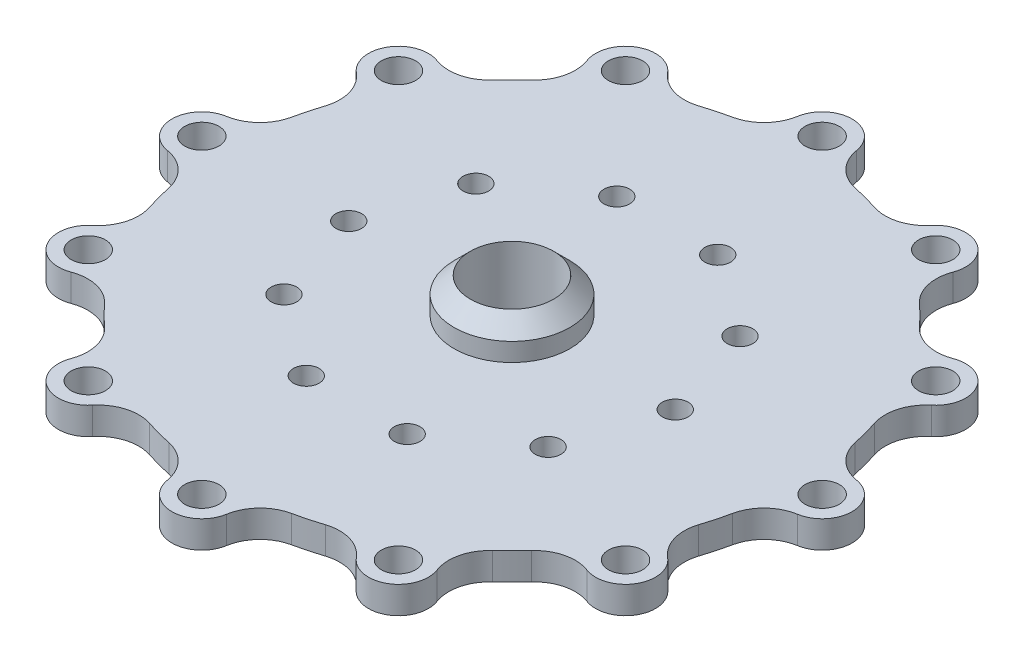
SolidWorks part; units mm, degrees
material "Nickel"
ref_plane "Front Plane" through (0, 0, 0) normal (0, 0, 1) x (1, 0, 0)
ref_plane "Top Plane" through (0, 0, 0) normal (0, 1, 0) x (1, 0, 0)
ref_plane "Right Plane" through (0, 0, 0) normal (1, 0, 0) x (0, 0, -1)
sketch "Sketch1" plane through (0, 0, 0) normal (0, 0, 1) x (1, 0, 0)
  line L0 (79.375, 10.6858) -> (79.375, 17.0358)
  line L1 (0, 0) -> (0, 52.0897) construction
  line L3 (79.375, 10.6858) -> (19.2253, 10.6858)
  line L4 (79.375, 17.0358) -> (13.5204, 17.0358)
  line L5 (9.7104, 25.1308) -> (9.7104, 0)
  line L6 (14.1453, -4.4348) -> (19.2253, -4.4348)
  line L10 (19.2253, -4.4348) -> (19.2253, 10.6858)
  line L11 (9.7104, 25.1308) -> (13.5204, 25.1308)
  line L12 (13.5204, 25.1308) -> (13.5204, 17.0358)
  line L15 (14.1453, -4.4348) -> (9.7104, 0)
  dimension "D1" = 79.375
  dimension "D2" = 9.7104
  dimension "D3" = 15.1206
  dimension "D4" = 6.35
  dimension "D5" = 19.2253
  dimension "D8" = 135
  dimension "D9" = 5.08
  dimension "D10" = 3.81
  dimension "D11" = 8.095
revolve "Revolve1" add sketch "Sketch1" angle 360 about L1
chamfer "Chamfer1" distance 3.81 angle 45 1 edges at (13.5204, 25.1308, 0)
hole_wizard "Hole2" positions "Sketch5" profile "Sketch6" legacy end condition up to next
sketch "Sketch5" plane through (0, 17.0358, 0) normal (0, 1, 0) x (1, 0, 0)
  line L0 (0, 0) -> (38.1, 0) construction
  point P0 (38.1, 0)
  dimension "D1" = 38.1
sketch "Sketch6" plane through (38.1, 17.0358, 0) normal (1, 0, 0) x (0, 0, 1)
  line L0 (0, 0) -> (0, 6.351)
  line L1 (0, 6.351) -> (3, 6.351)
  line L2 (3, 6.351) -> (3, 0)
  line L3 (3, 0) -> (0, 0)
  line L4 (0, 110) -> (0, -10) construction
  dimension "Diameter" = 6
  dimension "Depth" = 6.351
pattern_circular "CirPattern2" count 10 over 360 about axis through (0, 0, 0) along (0, 1, 0) of "Hole2"
hole_wizard "Hole4" positions "Sketch11" profile "Sketch13" legacy
sketch "Sketch11" plane through (0, 10.6858, 0) normal (0, 1, 0) x (1, 0, 0)
  line L0 (0, 0) -> (72.39, 0)
  point P0 (72.39, 0)
  dimension "D1" = 72.39
sketch "Sketch13" plane through (72.39, 10.6858, 0) normal (1, 0, 0) x (0, 0, -1)
  line L0 (0, 0) -> (0, 6.351)
  line L1 (0, 6.351) -> (4, 6.351)
  line L2 (4, 6.351) -> (4, 0)
  line L3 (4, 0) -> (0, 0)
  line L4 (0, 110) -> (0, -10) construction
  dimension "Diameter" = 8
  dimension "Depth" = 6.351
pattern_circular "CirPattern4" count 12 over 360 about axis through (0, 0, 0) along (0, 1, 0) of "Hole4"
sketch "Sketch17" plane through (0, 17.0358, 0) normal (0, 1, 0) x (1, 0, 0)
  arc A0 (79.375, 0) -> (73.5318, 6.891) centre (72.39, 0) ccw
  arc A1 (67.1259, 30.7981) -> (68.7408, 39.6875) centre (62.6916, 36.195) ccw
  arc A2 (65.7802, 14.2688) -> (64.1017, 20.533) centre (0, 0) ccw
  circle A3 centre (0, 0) radius 79.375 construction
  arc A4 (79.375, 0) -> (68.7408, 39.6875) centre (0, 0) ccw
  circle A5 centre (62.6916, 36.195) radius 4 construction
  arc A6 (65.7802, 14.2688) -> (73.5318, 6.891) centre (75.0888, 16.2879) ccw
  circle A7 centre (72.39, 0) radius 4 construction
  arc A8 (67.1259, 30.7981) -> (64.1017, 20.533) centre (73.1727, 23.4386) ccw
  dimension "D1" = 134.62
  dimension "D2" = 19.05
extrude "Cut-Extrude3" cut sketch "Sketch17" against normal up to next
pattern_circular "CirPattern5" count 12 over 360 about axis through (0, 0, 0) along (0, 1, 0) of "Cut-Extrude3"
